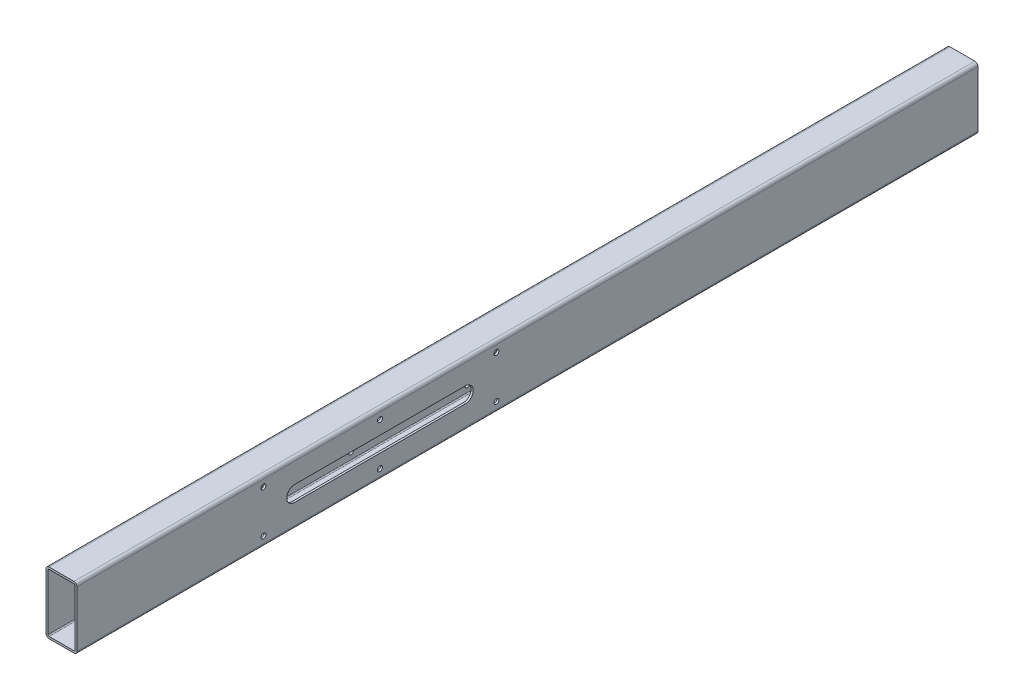
SolidWorks part; units mm, degrees
material "6061-T6 (SS)"
ref_plane "Front Plane" through (0, 0, 0) normal (0, 0, 1) x (1, 0, 0)
ref_plane "Top Plane" through (0, 0, 0) normal (0, 1, 0) x (1, 0, 0)
ref_plane "Right Plane" through (0, 0, 0) normal (1, 0, 0) x (0, 0, -1)
sketch "Sketch1" plane through (0, 0, 0) normal (0, 0, 1) x (1, 0, 0)
  line L1 (10.16, -25.4) -> (-10.16, -25.4)
  line L2 (12.7, -22.86) -> (12.7, 22.86)
  line L3 (10.16, 25.4) -> (-10.16, 25.4)
  line L4 (-12.7, -22.86) -> (-12.7, 22.86)
  line L5 (12.7, -25.4) -> (-12.7, 25.4) construction
  line L6 (12.7, 25.4) -> (-12.7, -25.4) construction
  arc A0 (-10.16, -25.4) -> (-12.7, -22.86) centre (-10.16, -22.86) cw
  arc A1 (10.16, -25.4) -> (12.7, -22.86) centre (10.16, -22.86) ccw
  arc A2 (12.7, 22.86) -> (10.16, 25.4) centre (10.16, 22.86) ccw
  arc A3 (-10.16, 25.4) -> (-12.7, 22.86) centre (-10.16, 22.86) ccw
  point P0 (0, 0)
  dimension "D3" = 2.54
  dimension "D1" = 25.4
  dimension "D2" = 50.8
extrude "Extrude-Thin1" add sketch "Sketch1" along normal mid plane 736.6 thin thin type one direction reverse wall 1.651
sketch "Sketch2" [suppressed] plane through (-12.7, 0, 0) normal (-1, 0, 0) x (0, 0, 1)
  line L0 (25.4, 0) -> (152.4, 0) construction
  line L1 (25.4, 6.35) -> (152.4, 6.35)
  line L2 (25.4, -6.35) -> (152.4, -6.35)
  line L3 (0, 22.86) -> (0, -22.86) construction
  arc A0 (25.4, 6.35) -> (25.4, -6.35) centre (25.4, 0) ccw
  arc A1 (152.4, -6.35) -> (152.4, 6.35) centre (152.4, 0) ccw
  point P3 (88.9, 0)
  dimension "D1" = 12.7
  dimension "D2" = 127
  dimension "D3" = 25.4
extrude "Cut-Extrude1" [suppressed] cut sketch "Sketch2" against normal through all
sketch "Sketch3" plane through (-12.7, 0, 0) normal (-1, 0, 0) x (0, 0, 1)
  line L0 (190.5, 0) -> (50.8, 0) construction
  line L1 (190.5, -6.35) -> (50.8, -6.35)
  line L2 (190.5, 6.35) -> (50.8, 6.35)
  line L3 (368.3, 22.86) -> (368.3, -22.86) construction
  arc A0 (190.5, -6.35) -> (190.5, 6.35) centre (190.5, 0) ccw
  arc A1 (50.8, 6.35) -> (50.8, -6.35) centre (50.8, 0) ccw
  point P3 (120.65, 0)
  dimension "D1" = 12.7
  dimension "D2" = 177.8
  dimension "D3" = 139.7
extrude "Cut-Extrude2" cut sketch "Sketch3" against normal through all
sketch "Sketch5" plane through (12.7, 0, 0) normal (1, 0, 0) x (0, 0, -1)
  circle A0 centre (-25.4, 17.399) radius 2.0193 construction
  circle A1 centre (-25.4, -17.399) radius 2.0193 construction
  circle A2 centre (-120.65, 17.399) radius 2.0193 construction
  circle A3 centre (-120.65, -17.399) radius 2.0193 construction
  circle A4 centre (-215.9, -17.399) radius 2.0193 construction
  circle A5 centre (-215.9, 17.399) radius 2.0193 construction
  circle A6 centre (-25.4, 17.399) radius 2.0193
  circle A7 centre (-25.4, -17.399) radius 2.0193
  circle A8 centre (-120.65, 17.399) radius 2.0193
  circle A9 centre (-120.65, -17.399) radius 2.0193
  circle A10 centre (-215.9, -17.399) radius 2.0193
  circle A11 centre (-215.9, 17.399) radius 2.0193
extrude "Cut-Extrude3" cut sketch "Sketch5" against normal through all
